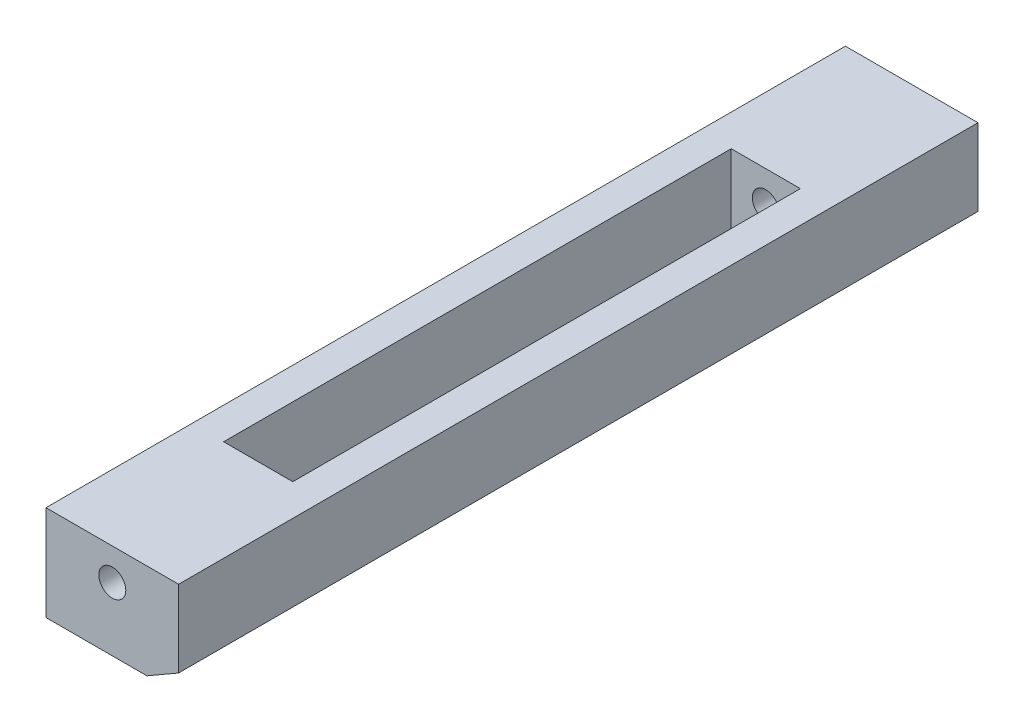
SolidWorks part; units mm, degrees
ref_plane "Front Plane" through (0, 0, 0) normal (0, 0, 1) x (1, 0, 0)
ref_plane "Top Plane" through (0, 0, 0) normal (0, 1, 0) x (1, 0, 0)
ref_plane "Right Plane" through (0, 0, 0) normal (1, 0, 0) x (0, 0, -1)
sketch "Sketch1" plane through (0, 0, 0) normal (0, 1, 0) x (1, 0, 0)
  line L1 (-6.6357, -40) -> (6.6357, -40)
  line L2 (-6.6357, -40) -> (-6.6357, 40)
  line L3 (-6.6357, 40) -> (6.6357, 40)
  line L4 (6.6357, -40) -> (6.6357, 40)
  line L5 (-6.6357, -40) -> (6.6357, 40) construction
  line L6 (-6.6357, 40) -> (6.6357, -40) construction
  line L11 (-3.4608, -25.4) -> (3.4607, -25.4)
  line L12 (-3.4608, -25.4) -> (-3.4608, 25.4)
  line L13 (-3.4608, 25.4) -> (3.4607, 25.4)
  line L14 (3.4607, -25.4) -> (3.4607, 25.4)
  line L15 (-3.4608, -25.4) -> (3.4607, 25.4) construction
  line L16 (-3.4608, 25.4) -> (3.4607, -25.4) construction
  point P0 (0, 0)
  point P6 (0, 0)
  dimension "D1" = 13.2715
  dimension "D2" = 80
  dimension "D3" = 3.175
  dimension "D4" = 50.8
extrude "Boss-Extrude1" add sketch "Sketch1" along normal blind 3.175 and the other way blind 6.35
sketch "Sketch4" plane through (0, 0, 40) normal (0, 0, 1) x (1, 0, 0)
  circle A0 centre (0, 0) radius 1.35
  dimension "D1" = 2.7
extrude "Cut-Extrude1" cut sketch "Sketch4" against normal through all
chamfer "Chamfer1" distance 3.175 angle 30 1 edges at (6.6357, -6.35, 0) first distance on face at (0, -6.35, 0)
equation "\"tightTol\"= 0.005in"
equation "\"normTol\"= 0.01in"
equation "\"looseTol\"= 0.02in"
equation "\"Fry height\"= 0.5in"
equation "\"Fry spacing\"= 0.5625in"
equation "\"Potato width\"= \"Fry spacing\" * 4"
equation "\"Potato length\"= 80mm"
equation "\"D1@Sketch1\"=\"Fry spacing\"-2*\"looseTol\""
equation "\"D2@Sketch1\"=\"Potato length\""
equation "\"D1@Sketch4\"=2.7mm"
